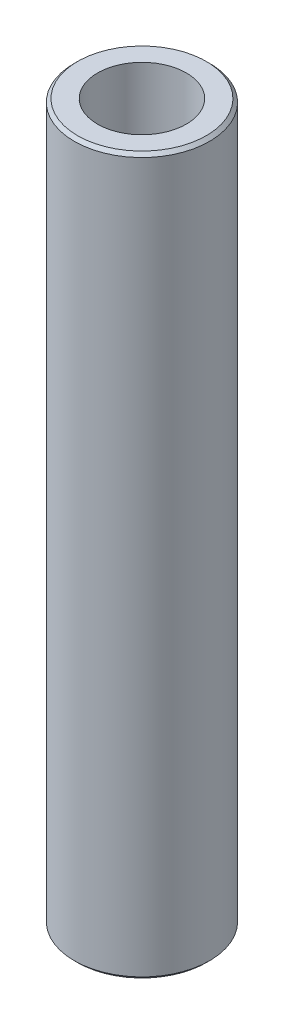
SolidWorks part; units mm, degrees
ref_plane "Front Plane" through (0, 0, 0) normal (0, 0, 1) x (1, 0, 0)
ref_plane "Top Plane" through (0, 0, 0) normal (0, 1, 0) x (1, 0, 0)
ref_plane "Right Plane" through (0, 0, 0) normal (1, 0, 0) x (0, 0, -1)
sketch "Sketch1" plane through (0, 0, 0) normal (0, 1, 0) x (1, 0, 0)
  circle A0 centre (0, 0) radius 45
  dimension "SHAFT_OD" = 90
extrude "Boss-Extrude1" add sketch "Sketch1" along normal blind 476.418
sketch "Sketch2" plane through (0, 0, 0) normal (0, 1, 0) x (1, 0, 0)
  circle A0 centre (0, 0) radius 29.5325
  dimension "BORE_D" = 59.0651
extrude "Cut-Extrude1" cut sketch "Sketch2" along normal through all
chamfer "Chamfer1" distance 2.1882 angle 45 2 edges at (0, 476.418, 45) (0, 0, 45)
